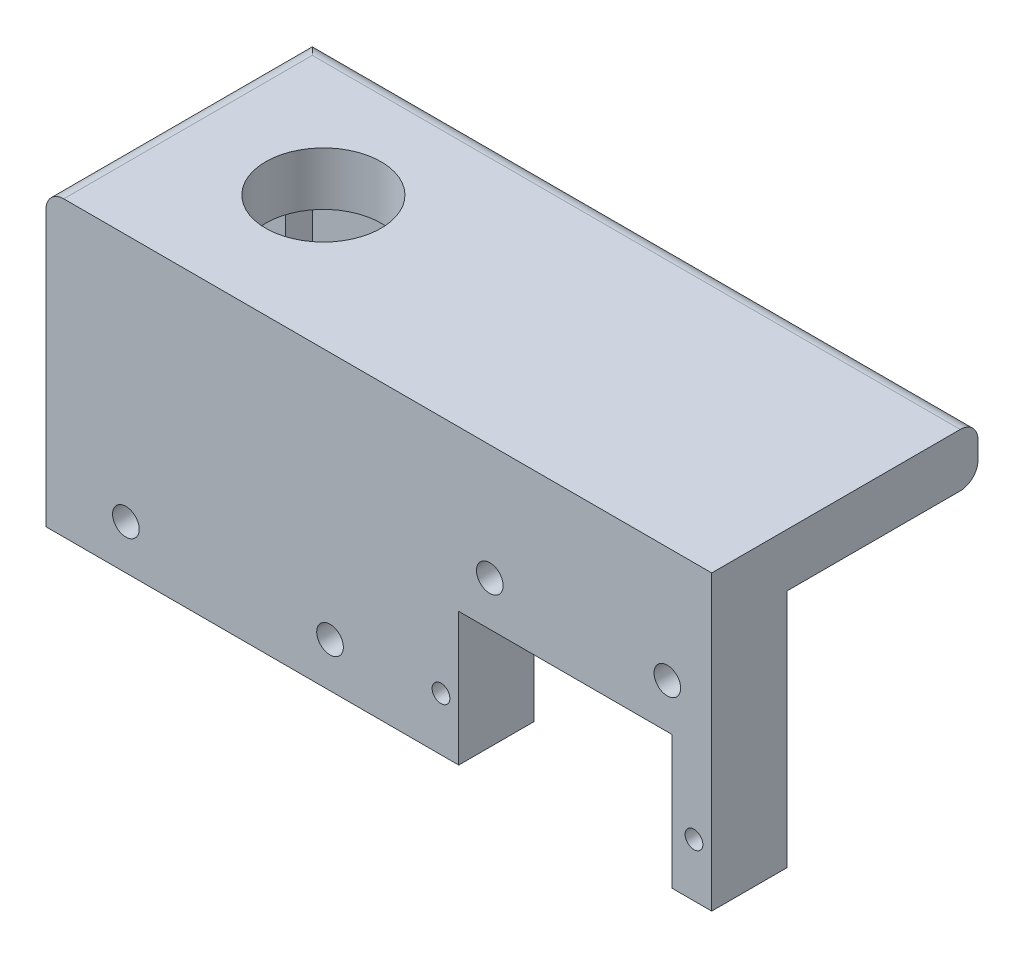
SolidWorks part; units mm, degrees
ref_plane "Front Plane" through (0, 0, 0) normal (0, 0, 1) x (1, 0, 0)
ref_plane "Top Plane" through (0, 0, 0) normal (0, 1, 0) x (1, 0, 0)
ref_plane "Right Plane" through (0, 0, 0) normal (1, 0, 0) x (0, 0, -1)
sketch "Sketch1" plane through (0, -4.342, 0) normal (0, -1, 0) x (1, 0, 0)
  line L0 (-40.9843, 28.2004) -> (-18.4843, 28.2004) construction
  line L1 (-11.5696, 28.2004) -> (-86.5696, 28.2004)
  line L2 (-11.5696, 28.2004) -> (-11.5696, -1.7996)
  line L3 (-11.5696, -1.7996) -> (-86.5696, -1.7996)
  line L4 (-86.5696, 28.2004) -> (-86.5696, -1.7996)
  dimension "D1" = 75
  dimension "D2" = 30
extrude "Boss-Extrude1" add sketch "Sketch1" along normal blind 6 contours L1 L4 L3 L2
sketch "Sketch2" plane through (0, -10.342, 0) normal (0, -1, 0) x (-1, 0, 0)
  line L1 (86.5696, 1.7996) -> (38.5696, 1.7996)
  line L2 (86.5696, 1.7996) -> (86.5696, -2.7004)
  line L3 (86.5696, -2.7004) -> (38.5696, -2.7004)
  line L4 (38.5696, 1.7996) -> (38.5696, -2.7004)
  line L5 (38.5696, 1.7996) -> (43.5696, 1.7996)
  line L6 (38.5696, 1.7996) -> (38.5696, -7.2004)
  line L7 (38.5696, -7.2004) -> (43.5696, -7.2004)
  line L8 (43.5696, 1.7996) -> (43.5696, -7.2004)
  line L9 (11.5696, -28.2004) -> (86.5696, -28.2004) construction
  line L10 (86.5696, 1.7996) -> (82.0696, 1.7996)
  line L11 (86.5696, 1.7996) -> (86.5696, -28.2004)
  line L12 (86.5696, -28.2004) -> (82.0696, -28.2004)
  line L13 (82.0696, 1.7996) -> (82.0696, -28.2004)
  line L14 (11.5696, -28.2004) -> (11.5696, 1.7996) construction
  line L15 (86.5696, -28.2004) -> (40.0696, -28.2004)
  line L16 (86.5696, -28.2004) -> (86.5696, -23.7004)
  line L17 (86.5696, -23.7004) -> (40.0696, -23.7004)
  line L18 (40.0696, -28.2004) -> (40.0696, -23.7004)
  line L19 (46.0696, -28.2004) -> (40.0696, -28.2004)
  line L20 (46.0696, -28.2004) -> (46.0696, -19.7004)
  line L21 (46.0696, -19.7004) -> (40.0696, -19.7004)
  line L22 (40.0696, -28.2004) -> (40.0696, -19.7004)
  line L24 (11.5696, -28.2004) -> (16.0696, -28.2004)
  line L25 (11.5696, -28.2004) -> (11.5696, -19.7004)
  line L26 (11.5696, -19.7004) -> (16.0696, -19.7004)
  line L27 (16.0696, -28.2004) -> (16.0696, -19.7004)
  dimension "D1" = 4.5
  dimension "D2" = 48
  dimension "D3" = 5
  dimension "D4" = 9
  dimension "D5" = 4.5
  dimension "D6" = 4.5
  dimension "D7" = 0
  dimension "D8" = 28.5
  dimension "D9" = 40.5
  dimension "D10" = 8.5
  dimension "D11" = 8.5
  dimension "D12" = 4.5
extrude "Boss-Extrude4" add sketch "Sketch2" along normal blind 27 contours L16 L15 L18 L17 | L2 L1 L4 L3 | L11 L10 L13 L12 | L6 L5 L8 L7 | L20 L19 L22 L21 | L25 L24 L27 L26
sketch "Sketch7" plane through (-38.5696, 0, 0) normal (1, 0, 0) x (0, 0, -1)
  line L1 (-7.2004, -37.342) -> (-2.7004, -37.342)
  line L2 (-7.2004, -37.342) -> (-7.2004, -22.342)
  line L3 (-7.2004, -22.342) -> (-2.7004, -22.342)
  line L4 (-2.7004, -37.342) -> (-2.7004, -22.342)
  dimension "D1" = 15
  dimension "D2" = 4.5
extrude "Cut-Extrude1" cut sketch "Sketch7" against normal blind 6
sketch "Sketch9" plane through (0, -4.342, 0) normal (0, 1, 0) x (1, 0, 0)
  line L1 (-86.5696, -28.2004) -> (-86.5696, 1.7996) construction
  line L2 (-11.5696, 1.7996) -> (-86.5696, 1.7996) construction
  circle A0 centre (-70.3196, -13.2004) radius 6.5
  dimension "D1" = 16.25
  dimension "D2" = 15
  dimension "D3" = 13
extrude "Cut-Extrude2" cut sketch "Sketch9" against normal blind 30
sketch "Sketch10" plane through (0, 0, 28.2004) normal (0, 0, 1) x (1, 0, 0)
  line L0 (-86.5696, -37.342) -> (-86.5696, -4.342) construction
  line L2 (-86.5696, -37.342) -> (-40.0696, -37.342) construction
  circle A0 centre (-77.5696, -32.342) radius 1.5
  dimension "D1" = 9
  dimension "D2" = 3
  dimension "D3" = 5
extrude "Cut-Extrude3" cut sketch "Sketch10" against normal blind 50
sketch "Sketch11" plane through (0, 0, 28.2004) normal (0, 0, 1) x (1, 0, 0)
  line L0 (-86.5696, -37.342) -> (-86.5696, -4.342) construction
  circle A0 centre (-54.5696, -32.342) radius 1.5
  circle A1 centre (-77.5696, -32.342) radius 1.5 construction
  dimension "D1" = 32
  dimension "D2" = 3
  dimension "D3" = 0
extrude "Cut-Extrude4" cut sketch "Sketch11" against normal blind 10
sketch "Sketch12" plane through (-86.5696, 0, 0) normal (-1, 0, 0) x (0, 0, 1)
  line L0 (-1.7996, -37.342) -> (28.2004, -37.342) construction
  line L1 (5.7004, -37.342) -> (20.7004, -37.342)
  line L2 (5.7004, -37.342) -> (5.7004, -11.342)
  line L3 (5.7004, -11.342) -> (20.7004, -11.342)
  line L4 (20.7004, -37.342) -> (20.7004, -11.342)
  line L5 (28.2004, -4.342) -> (-1.7996, -4.342) construction
  point P8 (13.2004, -4.342)
  dimension "D1" = 15
  dimension "D2" = 7.5
  dimension "D3" = 26
extrude "Cut-Extrude5" cut sketch "Sketch12" against normal blind 5
sketch "Sketch14" plane through (-40.0696, 0, 0) normal (1, 0, 0) x (0, 0, -1)
  line L1 (-19.7004, -22.342) -> (-28.2004, -22.342)
  line L2 (-19.7004, -22.342) -> (-19.7004, -10.342)
  line L3 (-19.7004, -10.342) -> (-28.2004, -10.342)
  line L4 (-28.2004, -22.342) -> (-28.2004, -10.342)
  dimension "D1" = 12
extrude "Boss-Extrude6" add sketch "Sketch14" along normal up to vertex (24 mm away) up to point (-16.0696, -10.342, 28.2004)
sketch "Sketch15" plane through (0, 0, 28.2004) normal (0, 0, 1) x (1, 0, 0)
  line L0 (-11.5696, -37.342) -> (-16.0696, -37.342) construction
  line L1 (-11.5696, -37.342) -> (-11.5696, -4.342) construction
  line L2 (-40.0696, -37.342) -> (-40.0696, -22.342) construction
  circle A0 centre (-13.5696, -31.342) radius 1
  circle A1 centre (-42.0696, -31.342) radius 1
  dimension "D1" = 2
  dimension "D2" = 6
  dimension "D3" = 2
  dimension "D4" = 0
  dimension "D5" = 2
  dimension "D6" = 2
extrude "Cut-Extrude6" cut sketch "Sketch15" against normal blind 11
sketch "Sketch16" plane through (0, 0, 19.7004) normal (0, 0, -1) x (-1, 0, 0)
  line L1 (11.5696, -37.342) -> (11.5696, -10.342) construction
  line L2 (16.0696, -22.342) -> (40.0696, -22.342) construction
  circle A0 centre (36.5696, -17.342) radius 1.5
  circle A1 centre (16.5696, -17.342) radius 1.5
  dimension "D1" = 3
  dimension "D2" = 3
  dimension "D3" = 5
  dimension "D4" = 5
  dimension "D5" = 5
  dimension "D6" = 20
extrude "Cut-Extrude7" cut sketch "Sketch16" against normal blind 11
fillet "Fillet1" radius 2 4 edges at (-86.5696, -4.342, 13.2004) (-25.0696, -10.342, -1.7996) (-49.0696, -4.342, -1.7996) (-38.5696, -23.842, -1.7996)
fillet "Fillet2" radius 1 3 edges at (-86.5696, -11.342, 13.2004) (-86.5696, -24.342, 5.7004) (-86.5696, -24.342, 20.7004)
